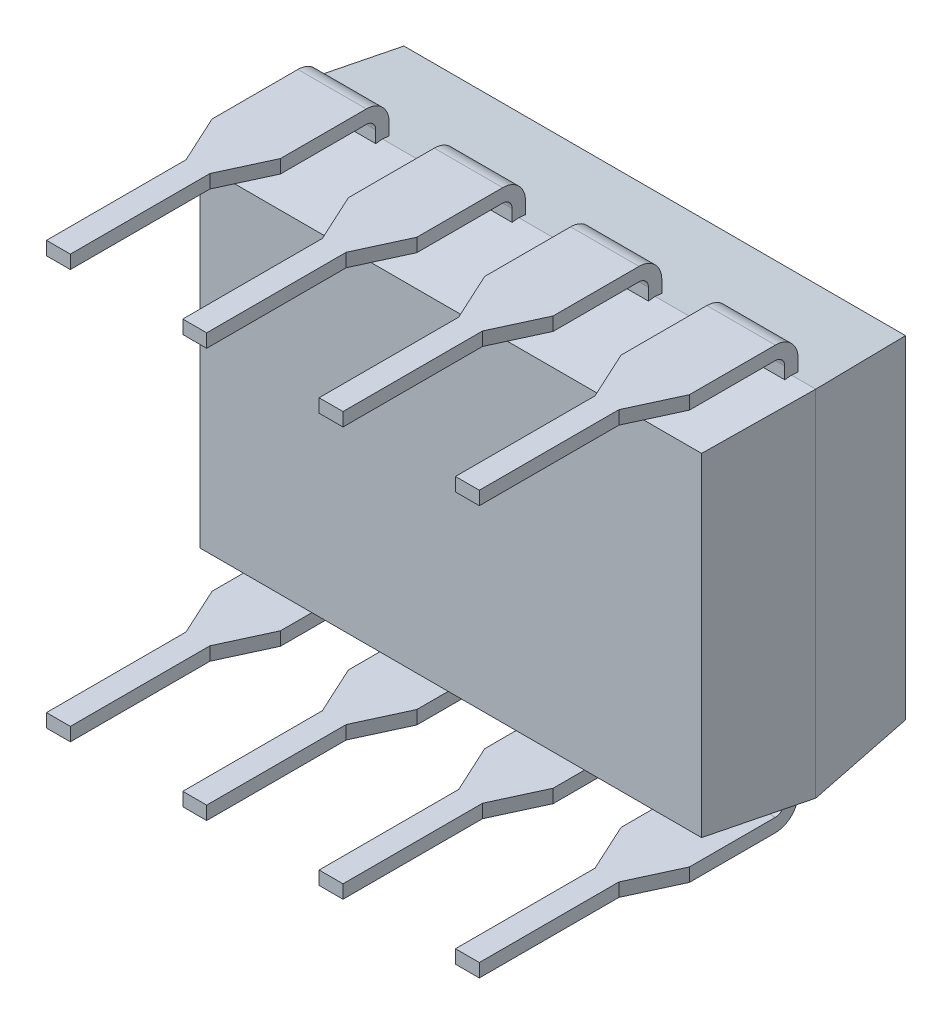
SolidWorks part; units mm, degrees
ref_plane "Plano frontal" through (0, 0, 0) normal (0, 0, 1) x (1, 0, 0)
ref_plane "Plano superior" through (0, 0, 0) normal (0, 1, 0) x (1, 0, 0)
ref_plane "Plano direito" through (0, 0, 0) normal (1, 0, 0) x (0, 0, -1)
sketch "Esboço1" plane through (0, 0, 0) normal (1, 0, 0) x (0, 0, -1)
  line L0 (0.9, 3.1) -> (0.9, -3.1)
  line L1 (0.9, -3.1) -> (2.8, -3.3)
  line L2 (2.8, -3.3) -> (4.7, -3.1)
  line L3 (4.7, -3.1) -> (4.7, 3.1)
  line L4 (4.7, 3.1) -> (2.8, 3.3)
  line L5 (2.8, 3.3) -> (0.9, 3.1)
  line L6 (2.8, 3.3) -> (2.8, -3.3) construction
  line L7 (4.7, 0) -> (2.8, 0) construction
  line L8 (2.8, 0) -> (0.9, 0) construction
  line L9 (0.9, 0) -> (0, 0) construction
  dimension "D1" = 6.6
  dimension "D2" = 6.2
  dimension "D3" = 3.8
  dimension "D4" = 0.9
extrude "Ressalto-extrusão1" add sketch "Esboço1" along normal mid plane 9.8
sketch "Esboço3" plane through (0, 0, 0) normal (0, 1, 0) x (1, 0, 0)
  line L0 (-4.9, 2.8) -> (-4.6699, 4.7268)
  line L1 (-4.6699, 4.7268) -> (-5.8363, 4.7268)
  line L2 (-5.8363, 4.7268) -> (-5.8363, 0.8732)
  line L3 (-5.8363, 0.8732) -> (-4.6699, 0.8732)
  line L4 (-4.6699, 0.8732) -> (-4.9, 2.8)
  line L5 (-5.8363, 2.8) -> (-4.9, 2.8) construction
  line L6 (-4.9, 0.9) -> (-4.9, 2.8) construction
  dimension "D1" = 6.81
  dimension "D2" = 3.8537
  dimension "D3" = 1.1665
extrude "Corte-extrusão2" cut sketch "Esboço3" against normal mid plane 7.1
mirror "Espelhar1" about plane through (0, 0, 0) normal (1, 0, 0) of "Corte-extrusão2"
sketch "Esboço8" plane through (0, 0, -4.7) normal (0, 0, -1) x (-1, 0, 0)
  line L0 (4.6731, -3.1) -> (4.6731, 3.1) construction
  circle A0 centre (4.6731, 0) radius 1
  dimension "D1" = 2
extrude "Corte-extrusão5" cut sketch "Esboço8" against normal blind 0.5
ref_plane "Plano1" through (0, 3.3, 0) normal (0, 1, 0) x (1, 0, 0)
sketch "Esboço6" plane through (0, 3.3, 0) normal (0, 1, 0) x (1, 0, 0)
  line L0 (-3.1725, 2.8) -> (0, 2.8) construction
  line L1 (-4.4475, 2.925) -> (-3.1725, 2.925)
  line L2 (-4.4475, 2.925) -> (-4.4475, 2.675)
  line L3 (-4.4475, 2.675) -> (-3.1725, 2.675)
  line L4 (-3.1725, 2.925) -> (-3.1725, 2.675)
  line L5 (4.9, 2.8) -> (-4.9, 2.8) construction
  line L6 (-3.81, 2.925) -> (-3.81, 2.675) construction
  dimension "D1" = 0.25
  dimension "D2" = 1.275
  dimension "D3" = 1.09
extrude "Ressalto-extrusão2" add sketch "Esboço6" along normal mid plane 0.05
sketch "Esboço7" plane through (0, 3.325, 0) normal (0, 1, 0) x (1, 0, 0)
  line L0 (-4.4475, 2.925) -> (-4.4475, 2.675) construction
  line L1 (-3.1725, 2.925) -> (-4.4475, 2.925) construction
  line L2 (-3.1725, 2.675) -> (-3.1725, 2.925) construction
  line L3 (-4.4475, 2.675) -> (-3.1725, 2.675) construction
  line L4 (-4.4475, 2.925) -> (-4.4475, 2.675)
  line L5 (-3.1725, 2.925) -> (-4.4475, 2.925)
  line L6 (-3.1725, 2.675) -> (-3.1725, 2.925)
  line L7 (-4.4475, 2.675) -> (-3.1725, 2.675)
  line L8 (-4.4475, 2.8) -> (-3.1725, 2.8) construction
sketch3d "3DSketch1"
  line L0 (-3.81, 3.325, -2.8) -> (-3.81, 3.51, -2.8)
  line L1 (-3.81, 3.325, -2.8) -> (-3.81, 0, -2.8) construction
  line L2 (-4.4475, 3.325, -2.8) -> (-3.1725, 3.325, -2.8) construction
  line L3 (-3.81, 3.81, -2.5) -> (-3.81, 3.81, 0)
  line L4 (-3.81, 0, -2.8) -> (0, 0, 0) construction
  arc A0 (-3.81, 3.51, -2.8) -> (-3.81, 3.81, -2.5) centre (-3.81, 3.51, -2.5) ccw
  point P5 (-3.51, 3.51, -2.5)
  dimension "D3" = 0.3
  dimension "D1" = 2.8
  dimension "D2" = 3.81
sweep "Varredura1" add profiles "Esboço7" path "3DSketch1"
sketch "Esboço9" plane through (0, 3.935, 0) normal (0, 1, 0) x (1, 0, 0)
  line L0 (-4.0325, 0) -> (-4.4475, 0.9)
  line L1 (-3.1725, 0) -> (-4.4475, 0) construction
  line L3 (-4.4475, 2.5) -> (-4.4475, 0) construction
  line L4 (-4.4475, 0.9) -> (-4.4475, -0.2)
  line L5 (-4.4475, -0.2) -> (-3.1725, -0.2)
  line L6 (-3.1725, -0.2) -> (-3.1725, 0.9)
  line L7 (-3.1725, 2.5) -> (-3.1725, 0) construction
  line L8 (-3.1725, 0.9) -> (-3.5875, 0)
  line L9 (-3.5875, 0) -> (-4.0325, 0)
  line L10 (-3.81, 0) -> (-3.81, 2.5) construction
  line L11 (-3.1725, 2.5) -> (-4.4475, 2.5) construction
  dimension "D1" = 0.9
  dimension "D2" = 0.445
  dimension "D3" = 0.2
extrude "Corte-extrusão6" cut sketch "Esboço9" against normal up to next (0.25 mm away)
sketch "Esboço10" plane through (0, 0, 0) normal (0, 0, 1) x (1, 0, 0)
  line L0 (-3.5875, 3.935) -> (-4.0325, 3.935) construction
  line L1 (-4.0325, 3.935) -> (-4.0325, 3.685) construction
  line L2 (-4.0325, 3.685) -> (-3.5875, 3.685) construction
  line L3 (-3.5875, 3.685) -> (-3.5875, 3.935) construction
  line L4 (-3.5875, 3.935) -> (-4.0325, 3.935)
  line L5 (-4.0325, 3.935) -> (-4.0325, 3.685)
  line L6 (-4.0325, 3.685) -> (-3.5875, 3.685)
  line L7 (-3.5875, 3.685) -> (-3.5875, 3.935)
extrude "Ressalto-extrusão3" add sketch "Esboço10" along normal blind 2.6
mirror "Espelhar2" about plane through (0, 0, 0) normal (0, 1, 0) of "Ressalto-extrusão3", "Corte-extrusão6", "Varredura1", "Ressalto-extrusão2"
pattern_linear "Padrão linear1" count 4 spacing 2.54 along (1, 0, 0) of "Ressalto-extrusão2", "Varredura1", "Corte-extrusão6", "Ressalto-extrusão3", "Espelhar2"
